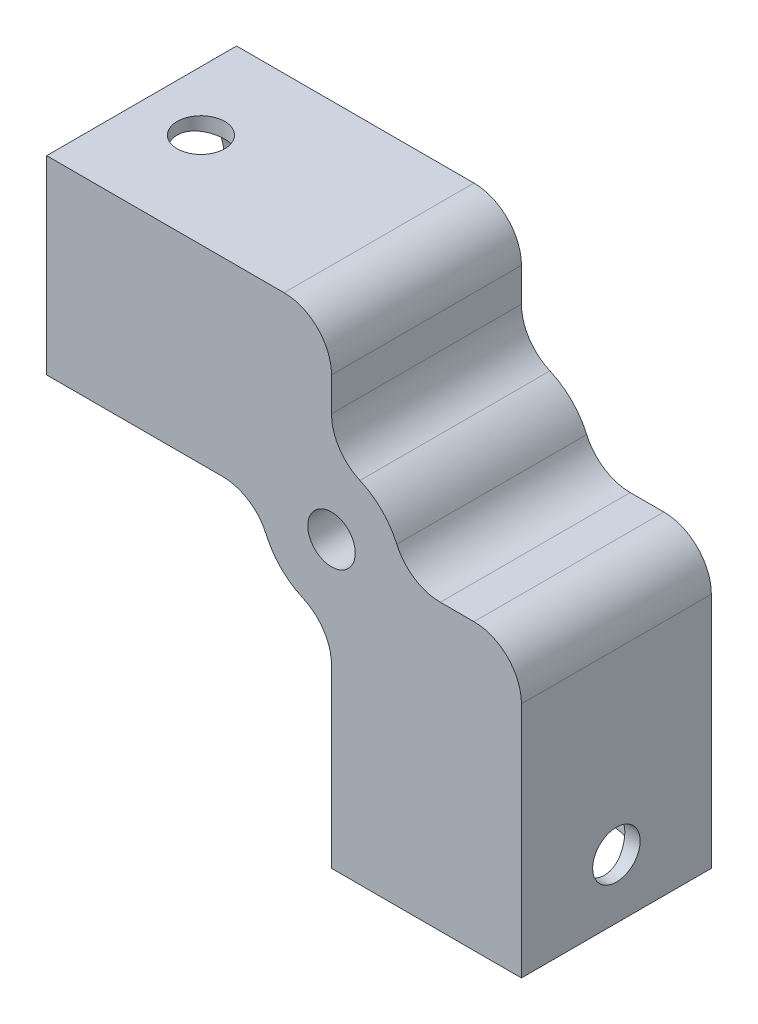
SolidWorks part; units mm, degrees
ref_plane "Front Plane" through (0, 0, 0) normal (0, 0, 1) x (1, 0, 0)
ref_plane "Top Plane" through (0, 0, 0) normal (0, 1, 0) x (1, 0, 0)
ref_plane "Right Plane" through (0, 0, 0) normal (1, 0, 0) x (0, 0, -1)
sketch "Sketch1" plane through (0, 0, 0) normal (0, 0, 1) x (1, 0, 0)
  line L0 (0, 0) -> (0, 8)
  line L1 (0, -55) -> (0, 55) construction
  line L2 (0, 8) -> (10, 8)
  line L6 (55, 0) -> (-55, 0) construction
  line L8 (20, -2) -> (20, -12)
  line L9 (20, -12) -> (12, -12)
  line L10 (12, -12) -> (12, -4.5826)
  line L11 (7.4174, 0) -> (0, 0)
  line L12 (0, 4) -> (50000, 4) construction
  line L13 (16, -12) -> (16, 49988) construction
  line L15 (12, 6) -> (12, 4.5826)
  line L18 (16.5826, 0) -> (18, 0)
  circle A0 centre (8, 4) radius 3.5
  circle A1 centre (16, -4) radius 3.5
  arc A7 (12, 6) -> (10, 8) centre (10, 6) ccw
  arc A8 (20, -2) -> (18, 0) centre (18, -2) ccw
  circle A9 centre (12, 0) radius 1
  arc A10 (9.2505, -1.2) -> (10.8, -2.7495) centre (12, 0) ccw
  arc A11 (14.7495, 1.2) -> (13.2, 2.7495) centre (12, 0) ccw
  arc A12 (9.2505, -1.2) -> (7.4174, 0) centre (7.4174, -2) ccw
  arc A13 (12, -4.5826) -> (10.8, -2.7495) centre (10, -4.5826) ccw
  arc A14 (13.2, 2.7495) -> (12, 4.5826) centre (14, 4.5826) cw
  arc A15 (16.5826, 0) -> (14.7495, 1.2) centre (16.5826, 2) cw
  point P17 (0, 4)
  point P20 (16, -12)
  point P32 (12, 4)
  point P35 (16, 0)
  point P40 (20, 0)
  point P43 (15, 0)
  dimension "D1" = 2
  dimension "D2" = 2
  dimension "D3" = 2
  dimension "D4" = 2
  dimension "D5" = 2
  dimension "D6" = 2
extrude "Boss-Extrude1" add sketch "Sketch1" along normal blind 8
sketch "Sketch5" plane through (0, 0, 0) normal (-1, 0, 0) x (0, 0, 1)
  circle A0 centre (4, 4) radius 3.5
extrude "Cut-Extrude1" cut sketch "Sketch5" against normal blind 8
sketch "Sketch6" plane through (0, -12, 0) normal (0, -1, 0) x (1, 0, 0)
  circle A0 centre (16, 4) radius 3.5
extrude "Cut-Extrude2" cut sketch "Sketch6" against normal blind 8
sketch "Sketch2" plane through (0, 0, 8) normal (0, 0, 1) x (1, 0, 0)
  circle A0 centre (8, 4) radius 3.5
  circle A1 centre (16, -4) radius 3.5
extrude "Boss-Extrude2" add sketch "Sketch2" against normal blind 0.5
sketch "Sketch4" plane through (0, 0, 0) normal (0, 0, -1) x (-1, 0, 0)
  circle A0 centre (-8, 4) radius 3.5
  circle A1 centre (-16, -4) radius 3.5
extrude "Boss-Extrude3" add sketch "Sketch4" against normal blind 0.5
sketch "Sketch7" plane through (0, 0, 0) normal (0, -1, 0) x (1, 0, 0)
  line L0 (0, 4) -> (2.5, 4) construction
  line L1 (0, 8) -> (0, 0) construction
  circle A0 centre (2.5, 4) radius 1
extrude "Cut-Extrude3" cut sketch "Sketch7" against normal blind 8
sketch "Sketch8" plane through (12, 0, 0) normal (-1, 0, 0) x (0, 0, 1)
  line L0 (4, -12) -> (4, -9.5) construction
  line L1 (8, -12) -> (0, -12) construction
  circle A0 centre (4, -9.5) radius 1
extrude "Cut-Extrude4" cut sketch "Sketch8" against normal blind 8
sketch "Sketch9" plane through (0, 0, 0) normal (0, -1, 0) x (1, 0, 0)
  circle A0 centre (2.5, 4) radius 2.5
  circle A1 centre (2.5, 4) radius 1
extrude "Boss-Extrude4" add sketch "Sketch9" along normal blind 1
sketch "Sketch10" plane through (12, 0, 0) normal (-1, 0, 0) x (0, 0, 1)
  circle A0 centre (4, -9.5) radius 1
  circle A1 centre (4, -9.5) radius 2.5
extrude "Boss-Extrude5" add sketch "Sketch10" along normal blind 1
